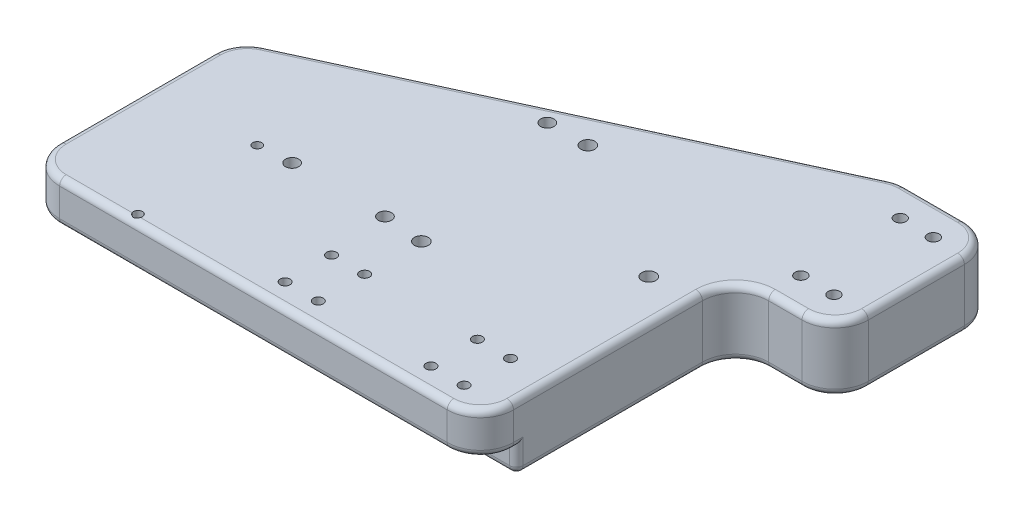
SolidWorks part; units mm, degrees
ref_plane "前视基准面" through (0, 0, 0) normal (0, 0, 1) x (1, 0, 0)
ref_plane "上视基准面" through (0, 0, 0) normal (0, 1, 0) x (1, 0, 0)
ref_plane "右视基准面" through (0, 0, 0) normal (1, 0, 0) x (0, 0, -1)
sketch "草图1" plane through (0, 0, 0) normal (0, 1, 0) x (1, 0, 0)
  line L1 (-83.5, -63) -> (83.5, -63)
  line L2 (-83.5, -63) -> (-83.5, 63)
  line L3 (-83.5, 63) -> (83.5, 63)
  line L4 (83.5, -63) -> (83.5, 63)
  line L5 (-83.5, -63) -> (83.5, 63) construction
  line L6 (-83.5, 63) -> (83.5, -63) construction
  point P0 (0, 0)
  dimension "D1" = 167
  dimension "D2" = 126
extrude "凸台-拉伸1" add sketch "草图1" along normal blind 20
sketch "草图2" plane through (0, 20, 0) normal (0, 1, 0) x (1, 0, 0)
  circle A0 centre (73.7019, 53.449) radius 1.75 construction
  circle A1 centre (63.7019, 53.449) radius 1.75 construction
  circle A2 centre (73.7019, 23.449) radius 1.75 construction
  circle A3 centre (63.7019, 23.449) radius 1.75 construction
  circle A4 centre (41.5449, -56) radius 1.5 construction
  circle A5 centre (31.5449, -56) radius 1.5 construction
  circle A6 centre (41.5449, -42) radius 1.5 construction
  circle A7 centre (31.5449, -42) radius 1.5 construction
  circle A8 centre (-2.4551, -56) radius 1.5 construction
  circle A9 centre (-12.4551, -56) radius 1.5 construction
  circle A10 centre (-2.4551, -42) radius 1.5 construction
  circle A11 centre (-12.4551, -42) radius 1.5 construction
  circle A16 centre (41.0097, 0.2556) radius 2.1 construction
  circle A17 centre (-2.4903, -24.8591) radius 2.1 construction
  circle A18 centre (-2.4903, 25.3703) radius 2.1 construction
  circle A19 centre (73.7019, 53.449) radius 1.75
  circle A20 centre (63.7019, 53.449) radius 1.75
  circle A21 centre (73.7019, 23.449) radius 1.75
  circle A22 centre (63.7019, 23.449) radius 1.75
  circle A23 centre (41.5449, -56) radius 1.5
  circle A24 centre (31.5449, -56) radius 1.5
  circle A25 centre (41.5449, -42) radius 1.5
  circle A26 centre (31.5449, -42) radius 1.5
  circle A27 centre (-2.4551, -56) radius 1.5
  circle A28 centre (-12.4551, -56) radius 1.5
  circle A29 centre (-2.4551, -42) radius 1.5
  circle A30 centre (-12.4551, -42) radius 1.5
  circle A35 centre (41.0097, 0.2556) radius 2.1
  circle A36 centre (-2.4903, -24.8591) radius 2.1
  circle A37 centre (-2.4903, 25.3703) radius 2.1
extrude "切除-拉伸1" cut sketch "草图2" against normal through all
sketch "草图3" plane through (0, 20, 0) normal (0, 1, 0) x (1, 0, 0)
  line L0 (83.5, 14) -> (53.4549, 14)
  line L1 (83.5, -63) -> (83.5, 63) construction
  line L2 (100.4549, 14) -> (56.4549, 14) construction
  line L3 (53.4549, 72.4008) -> (53.4549, -71.5992) construction
  line L4 (53.4549, 14) -> (53.4549, -77.8428)
  line L5 (53.4549, -77.8428) -> (91.2519, -77.8428)
  line L6 (91.2519, -77.8428) -> (91.2519, 0)
  line L7 (91.2519, 0) -> (87.0723, 7.2024)
  line L8 (87.0723, 7.2024) -> (85.0037, 10.7671)
  line L9 (85.0037, 10.7671) -> (83.5, 14)
extrude "切除-拉伸2" cut sketch "草图3" against normal through all
sketch "草图4" plane through (0, 20, 0) normal (0, 1, 0) x (1, 0, 0)
  line L8 (-83.5, 0) -> (53.4549, 63)
  line L9 (-83.5, 63) -> (-83.5, -63) construction
  line L10 (83.5, 63) -> (-83.5, 63) construction
  line L11 (53.4549, 72.4008) -> (53.4549, -71.5992) construction
  line L12 (53.4549, 63) -> (-20.5005, 68.6814)
  line L13 (-20.5005, 68.6814) -> (-84.2009, 68.6814)
  line L14 (-84.2009, 68.6814) -> (-88.4003, 40.356)
  line L15 (-88.4003, 40.356) -> (-83.5, 0)
  arc A0 (-85.6951, 69.5508) -> (-83.6951, 69.5508) centre (-84.6951, 69.5508) ccw construction
extrude "切除-拉伸4" cut sketch "草图4" against normal through all
sketch "草图7" plane through (0, 0, 0) normal (0, -1, 0) x (1, 0, 0)
  line L3 (-12.4551, 42) -> (-2.4551, 42) construction
  line L4 (-12.4551, 47) -> (-2.4551, 47)
  line L5 (-12.4551, 37) -> (-2.4551, 37)
  line L6 (31.5449, 56) -> (41.5449, 56) construction
  line L9 (31.5449, 42) -> (42.0238, 42) construction
  line L10 (31.5449, 47) -> (42.0238, 47)
  line L11 (31.5449, 37) -> (42.0238, 37)
  arc A6 (-12.4551, 47) -> (-12.4551, 37) centre (-12.4551, 42) ccw
  arc A7 (-2.4551, 37) -> (-2.4551, 47) centre (-2.4551, 42) ccw
  arc A10 (31.5449, 47) -> (31.5449, 37) centre (31.5449, 42) ccw
  arc A11 (42.0238, 37) -> (42.0238, 47) centre (42.0238, 42) ccw
  point P16 (-6.9762, 56)
  point P21 (-7.4551, 42)
  point P30 (37.0238, 56)
  point P39 (36.7843, 42)
  dimension "D7" = 5
  dimension "D8" = 5
extrude "切除-拉伸5" cut sketch "草图7" against normal blind 4
fillet "圆角1" radius 10 7 edges at (53.4549, 10, 63) (-83.5, 10, 63) (-83.5, 10, 0) (53.4549, 10, -63) (53.4549, 10, -14) (83.5, 10, -14) (83.5, 10, -63)
sketch "草图8" plane through (53.4549, 0, 0) normal (1, 0, 0) x (0, 0, -1)
  line L0 (-63, 7.5) -> (-56.3102, 7.5)
  line L2 (-63, 0) -> (-63, 20) construction
  line L3 (-56.3102, 7.5) -> (-56.3102, -1.2223)
  line L4 (-56.3102, -1.2223) -> (-67.0848, -1.2223)
  line L5 (-67.0848, -1.2223) -> (-67.0848, 7.5)
  line L6 (-67.0848, 7.5) -> (-63, 7.5)
  line L7 (4, 0) -> (-53, 0) construction
  dimension "D1" = 7.5
extrude "切除-拉伸6" cut sketch "草图8" against normal blind 155
sketch "草图9" plane through (0, 0, 0) normal (0, -1, 0) x (1, 0, 0)
  line L0 (-11.9762, 52.1368) -> (54.8691, 52.1368)
  line L1 (54.8691, 52.1368) -> (53.8581, 70.8007)
  line L2 (53.8581, 70.8007) -> (-42.6501, 70.8007)
  line L3 (-42.6501, 70.8007) -> (-92.7896, 67.4189)
  line L4 (-92.7896, 67.4189) -> (-84.788, 52.1368)
  line L5 (-84.788, 52.1368) -> (-11.9762, 52.1368)
extrude "切除-拉伸7" cut sketch "草图9" against normal blind 7.5
sketch "草图13" plane through (0, 20, 0) normal (0, 1, 0) x (1, 0, 0)
  circle A0 centre (-14.4903, 25.144) radius 2
  circle A1 centre (-14.4903, -23.856) radius 2
  circle A3 centre (-2.4903, 25.3703) radius 2.1 construction
  circle A5 centre (-2.4903, -24.8591) radius 2.1 construction
  circle A6 centre (-42.4903, -23.856) radius 2
  dimension "D1" = 12
  dimension "D2" = 4
  dimension "D3" = 49
  dimension "D4" = 4
  dimension "D5" = 12
  dimension "D6" = 28
  dimension "D7" = 4
extrude "切除-拉伸9" cut sketch "草图13" against normal blind 67
sketch "草图15" plane through (0, 0, 0) normal (0, -1, 0) x (1, 0, 0)
  arc A0 (-53.7074, 60.495) -> (-51.0074, 60.495) centre (-52.3574, 60.495) ccw construction
  arc A1 (-51.0074, 60.495) -> (-53.7074, 60.495) centre (-52.3574, 60.495) ccw construction
  arc A2 (-53.7074, 24.495) -> (-51.0074, 24.495) centre (-52.3574, 24.495) ccw construction
  arc A3 (-51.0074, 24.495) -> (-53.7074, 24.495) centre (-52.3574, 24.495) ccw construction
  arc A4 (-53.7074, 60.495) -> (-51.0074, 60.495) centre (-52.3574, 60.495) ccw
  arc A5 (-51.0074, 60.495) -> (-53.7074, 60.495) centre (-52.3574, 60.495) ccw
  arc A6 (-53.7074, 24.495) -> (-51.0074, 24.495) centre (-52.3574, 24.495) ccw
  arc A7 (-51.0074, 24.495) -> (-53.7074, 24.495) centre (-52.3574, 24.495) ccw
extrude "切除-拉伸10" cut sketch "草图15" against normal through all
sketch "草图16" plane through (0, 0, 0) normal (0, -1, 0) x (1, 0, 0)
  circle A0 centre (-14.4903, 23.856) radius 4
  circle A1 centre (-14.4903, -25.144) radius 4
  circle A2 centre (-42.4903, 23.856) radius 4
  circle A3 centre (-52.3574, 24.495) radius 3
  dimension "D1" = 8
  dimension "D2" = 8
  dimension "D3" = 8
  dimension "D4" = 6
extrude "切除-拉伸11" cut sketch "草图16" against normal blind 6
fillet "圆角2" radius 2 8 edges at (53.4549, 7.5, 52.5684) (-83.5, 7.5, 52.5684) (-80.5711, 7.5, 60.0711) (-15.0226, 7.5, 63) (-83.5, 3.75, 52.1368) (50.526, 7.5, 60.0711) (53.4549, 3.75, 52.1368) (-15.0226, 0, 52.1368)
fillet "圆角3" radius 2 27 edges at (52.8691, 0.5858, 51.551) (53.4549, 0, 23.0684) (56.3838, 0, -11.0711) (68.4774, 0, -14) (80.5711, 0, -16.9289) (-82.9142, 0.5858, 51.551) (-83.5, 0, 28.272) (-81.9199, 0, 1.0124) (-13.1068, 0, -32.3813) (53.5056, 0, -62.7685) (64.5723, 0, -63) (80.5711, 0, -60.0711) (80.5711, 20, -16.9289) (68.4774, 20, -14) (56.3838, 20, -11.0711) (53.4549, 20, 24.5) (50.526, 20, 60.0711) (-15.0226, 20, 63) (-80.5711, 20, 60.0711) (-83.5, 20, 29.7036) (-81.9199, 20, 1.0124) (-13.1068, 20, -32.3813) (53.5056, 20, -62.7685) (64.5723, 20, -63) (80.5711, 20, -60.0711) (83.5, 0, -38.5) (83.5, 20, -38.5)
